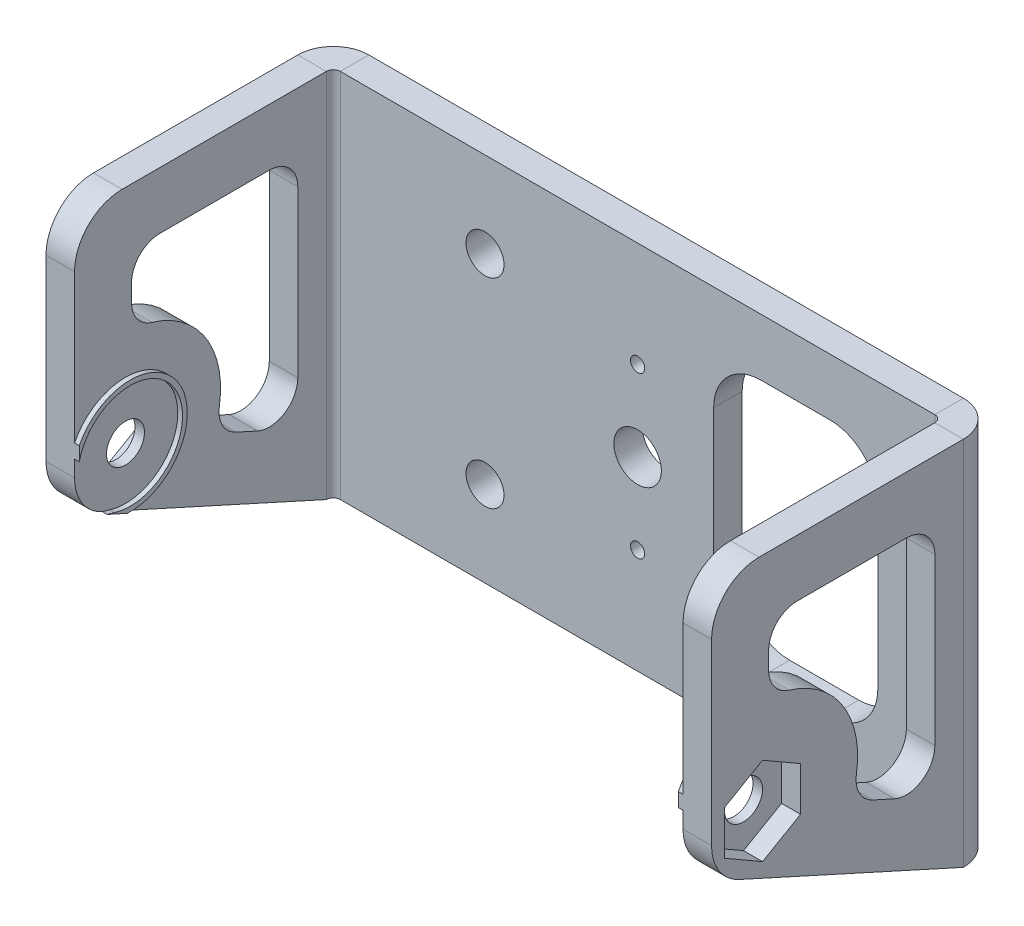
SolidWorks part; units mm, degrees
note: The reader was unsure of these and kept them because the rebuilt part matched: flange length of "Aresta-Flange1"; shared geometry of "Esboço13<3>".
ref_plane "Plano frontal" through (0, 0, 0) normal (0, 0, 1) x (1, 0, 0)
ref_plane "Plano superior" through (0, 0, 0) normal (0, 1, 0) x (1, 0, 0)
ref_plane "Plano direito" through (0, 0, 0) normal (1, 0, 0) x (0, 0, -1)
sketch "Esboço1" plane through (0, 0, 0) normal (0, 0, 1) x (1, 0, 0)
  line L1 (-37.0063, 15.0091) -> (26.9937, 15.0091)
  line L2 (-37.0063, 15.0091) -> (-37.0063, -23.9909)
  line L3 (-37.0063, -23.9909) -> (26.9937, -23.9909)
  line L4 (26.9937, 15.0091) -> (26.9937, -23.9909)
  dimension "D1" = 64
  dimension "D2" = 39
base flange "Flange-base1" sketch "Esboço1" thickness 3 reverse thickness direction no parameters "D1"=0.7366
sketch "Esboço6" plane through (0, 0, 0) normal (0, 0, 1) x (1, 0, 0)
  line L0 (-37.0063, -23.9909) -> (26.9937, 15.0091) construction
  line L1 (-21.0563, 6.0091) -> (11.0437, 6.0091)
  line L2 (-21.0563, 6.0091) -> (-21.0563, -14.9909)
  line L3 (-21.0563, -14.9909) -> (11.0437, -14.9909)
  line L4 (11.0437, 6.0091) -> (11.0437, -14.9909)
  line L5 (-37.0063, 15.0091) -> (26.9937, -23.9909) construction
  line L6 (26.9937, 15.0091) -> (-37.0063, 15.0091) construction
  line L7 (-37.0063, -23.9909) -> (26.9937, -23.9909) construction
  line L8 (-5.0063, 15.0091) -> (-5.0063, -23.9909) construction
  line L9 (-5.0063, 3.5238) -> (-5.0063, 12.5238) construction
  line L10 (-6.5063, 3.5238) -> (-6.5063, 12.5238)
  line L11 (-3.5063, 3.5238) -> (-3.5063, 12.5238)
  line L12 (-37.0063, -4.4909) -> (26.9937, -4.4909) construction
  line L13 (-37.0063, 15.0091) -> (-37.0063, -23.9909) construction
  line L14 (26.9937, -23.9909) -> (26.9937, 15.0091) construction
  line L15 (-5.0063, -12.5057) -> (-5.0063, -21.5057) construction
  line L16 (-6.5063, -12.5057) -> (-6.5063, -21.5057)
  line L17 (-3.5063, -12.5057) -> (-3.5063, -21.5057)
  circle A0 centre (-21.0563, 6.0091) radius 2
  circle A1 centre (-21.0563, -14.9909) radius 2
  circle A2 centre (11.0437, -14.9909) radius 2
  circle A3 centre (11.0437, 6.0091) radius 2
  circle A4 centre (-5.0063, -4.4909) radius 2.5
  arc A5 (-6.5063, 3.5238) -> (-3.5063, 3.5238) centre (-5.0063, 3.5238) ccw
  arc A6 (-3.5063, 12.5238) -> (-6.5063, 12.5238) centre (-5.0063, 12.5238) ccw
  arc A7 (-6.5063, -12.5057) -> (-3.5063, -12.5057) centre (-5.0063, -12.5057) cw
  arc A8 (-3.5063, -21.5057) -> (-6.5063, -21.5057) centre (-5.0063, -21.5057) cw
  circle A9 centre (-5.0063, -12.9409) radius 0.75
  circle A10 centre (-5.0063, 3.9591) radius 0.75
  point P18 (-5.0063, 8.0238)
  point P31 (-5.0063, -17.0057)
  dimension "D5" = 1.5
  dimension "D1" = 15.95
  dimension "D2" = 5
  dimension "D3" = 9
  dimension "D4" = 9
  dimension "D6" = 8.45
extrude "Corte-extrusão1" cut sketch "Esboço6" against normal blind 10 contours L1 A0 L2 | L2 A1 L3 | L3 A1 L2 | A4 | A9 | A10 | L2 A0 L1 | L16 A8 L17 A7
edge flange "Aresta-Flange1" sketch "Esboço11" flange profiles "Esboço11", "Esboço12" flange angle 90 flange length 30.22 flange position material outside bend radius 0.7366 thickness 3 parameters "D6"=10, "D8"=1
sketch "Esboço11" plane through (26.9937, 0, 0) normal (1, 0, 0) x (0, 1, 0)
  line L0 (-23.9909, 0) -> (15.0091, 0) construction
  line L1 (-23.9909, 0) -> (15.0091, 0)
  line L2 (-23.9909, 0) -> (-23.9909, 27.22)
  line L3 (-23.9909, 27.22) -> (15.0091, 27.22)
  line L4 (15.0091, 27.22) -> (15.0091, 0)
  dimension "D1" = 27.22
sketch "Esboço12" plane through (-37.0063, 0, 0) normal (-1, 0, 0) x (0, -1, 0)
  line L0 (-15.0091, 0) -> (23.9909, 0) construction
  line L1 (-15.0091, 0) -> (23.9909, 0)
  line L2 (-15.0091, 0) -> (-15.0091, 27.22)
  line L3 (-15.0091, 27.22) -> (23.9909, 27.22)
  line L4 (23.9909, 27.22) -> (23.9909, 0)
bend "DobradeAresta1" bend radius 0.7366 bend angle 90 parameters "D5"=1
bend "DobradeAresta2" bend radius 0.7366 bend angle 90 parameters "D5"=2
sketch "Esboço13" plane through (-40.0063, 0, 0) normal (-1, 0, 0) x (0, 0, 1)
  line L0 (0.7366, -23.9909) -> (27.22, -11.9909) construction
  line L1 (27.22, -23.9909) -> (27.22, 15.0091) construction
  line L2 (27.22, -11.9909) -> (0.7366, 15.0091) construction
  line L3 (0.7366, -23.9909) -> (27.22, -23.9909)
  line L4 (27.22, -23.9909) -> (27.22, -11.9909)
  line L5 (27.22, -11.9909) -> (0.7366, -23.9909)
  line L7 (17.86, -10.5964) -> (21.86, -12.9058)
  line L8 (21.86, -12.9058) -> (25.86, -10.5964)
  line L9 (25.86, -10.5964) -> (25.86, -5.9776)
  line L10 (25.86, -5.9776) -> (21.86, -3.6682)
  line L11 (21.86, -3.6682) -> (17.86, -5.9776)
  line L12 (17.86, -5.9776) -> (17.86, -10.5964)
  circle A0 centre (21.86, -8.287) radius 2
  circle A2 centre (21.86, -8.287) radius 4 construction
  point P12 (15.8204, -3.8404)
  dimension "D3" = 4
  dimension "D6" = 8
  dimension "D1" = 12
  dimension "D2" = 5.36
  dimension "D7" = 7.5
  dimension "D8" = 3.7039
extrude "Corte-extrusão2" cut sketch "Esboço13" against normal up to surface (70 mm away) contours A0 | L5 L3 L4 normal cut yes up to face at (29.9937, -4.4909, 13.9783)
fillet "Filete1" radius 5 4 edges at (28.4937, -11.9909, 27.22) (28.4937, 15.0091, 27.22) (-38.5063, -11.9909, 27.22) (-38.5063, 15.0091, 27.22)
extrude "Cut-Extrude1" cut sketch "Esboço13<3>" against normal blind 2 contours L11 L12 L7 L8 L9 L10 A0 normal cut yes
sketch "Esboço13<3>" plane through (-40.0063, 0, 0) normal (-1, 0, 0) x (0, 0, 1) same geometry as "Esboço13"
ref_plane "Plane1" through (-5.0063, 0, 0) normal (-1, 0, 0) x (0, -1, 0)
sketch "Sketch7" plane through (-37.0063, 0, 0) normal (1, 0, 0) x (0, 0, -1)
  line L0 (-24.2836, -13.3215) -> (-22.1704, -14.279)
  line L2 (-0.7366, -23.9909) -> (-24.2836, -13.3215) construction
  line L4 (-27.22, -8.7672) -> (-27.22, -5.5906)
  line L5 (-27.22, -8.7672) -> (-27.22, 10.0091) construction
  arc A0 (-22.1704, -14.279) -> (-27.22, -5.5906) centre (-21.86, -8.287) ccw
  arc A1 (-23.546, -13.5222) -> (-27.22, -7.054) centre (-21.86, -8.287) ccw
  arc A2 (-27.22, -8.7672) -> (-24.2836, -13.3215) centre (-22.22, -8.7672) ccw construction
  arc A3 (-27.22, -8.7672) -> (-24.2836, -13.3215) centre (-22.22, -8.7672) ccw
  arc A4 (-22.4908, -13.7507) -> (-24.2836, -13.3215) centre (-19.3008, 3.5311) cw
  dimension "D1" = 12
  dimension "D2" = 0.5
extrude "Boss-Extrude1" add sketch "Sketch7" along normal blind 0.5 contours A1 A4 L2 A0 A3
mirror "Mirror1" about plane through (-5.0063, 0, 0) normal (-1, 0, 0) of "Boss-Extrude1", "Cut-Extrude1"
sketch "Sketch15" plane through (0, 0, 0) normal (0, 0, 1) x (1, 0, 0)
  line L0 (26.2571, 15.0091) -> (-36.2697, 15.0091) construction
  line L1 (2.9937, 9.0091) -> (20.2571, 9.0091)
  line L2 (2.9937, 9.0091) -> (2.9937, -17.9909)
  line L3 (2.9937, -17.9909) -> (20.2571, -17.9909)
  line L4 (20.2571, 9.0091) -> (20.2571, -17.9909)
  line L5 (-36.2697, -23.9909) -> (26.2571, -23.9909) construction
  line L6 (26.2571, 15.0091) -> (26.2571, -23.9909) construction
  circle A0 centre (-5.0063, -4.4909) radius 2.5 construction
  dimension "D3" = 8
  dimension "D1" = 6
  dimension "D2" = 6
  dimension "D4" = 6
extrude "Cut-Extrude2" cut sketch "Sketch15" against normal up to surface (3 mm away) normal cut yes up to face at (-19.0563, 6.0091, -3)
fillet "Fillet1" radius 5 4 edges at (20.2571, -17.9909, -1.5) (2.9937, -17.9909, -1.5) (2.9937, 9.0091, -1.5) (20.2571, 9.0091, -1.5)
sketch "Sketch16" plane through (29.9937, 0, 0) normal (1, 0, 0) x (0, 0, -1)
  line L0 (-27.22, 10.0091) -> (-27.22, -8.7672) construction
  line L1 (-21.22, 9.0091) -> (-3.7366, 9.0091)
  line L2 (-21.22, 9.0091) -> (-21.22, 1.6925)
  line L3 (-12.5884, -12.0335) -> (-3.7366, -16.0444)
  line L4 (-3.7366, 9.0091) -> (-3.7366, -16.0444)
  line L5 (-0.7366, 15.0091) -> (-22.22, 15.0091) construction
  line L6 (-0.7366, 15.0091) -> (-0.7366, -23.9909) construction
  line L7 (-0.7366, -23.9909) -> (-24.2836, -13.3215) construction
  arc A0 (-12.5884, -12.0335) -> (-21.22, 1.6925) centre (-21.86, -8.287) ccw
  arc A1 (-22.1704, -14.279) -> (-27.22, -5.5906) centre (-21.86, -8.287) ccw construction
  dimension "D4" = 4
  dimension "D1" = 6
  dimension "D2" = 6
  dimension "D3" = 3
  dimension "D5" = 6
extrude "Cut-Extrude3" cut sketch "Sketch16" against normal up to surface (70 mm away) normal cut yes up to face at (-40.0063, -8.287, 21.86)
fillet "Fillet2" radius 3 10 edges at (-38.5063, 9.0091, 3.7366) (-38.5063, -16.0444, 3.7366) (-38.5063, -12.0335, 12.5884) (-38.5063, 1.6925, 21.22) (-38.5063, 9.0091, 21.22) (28.4937, -12.0335, 12.5884) (28.4937, -16.0444, 3.7366) (28.4937, 1.6925, 21.22) (28.4937, 9.0091, 21.22) (28.4937, 9.0091, 3.7366)
sketch "Curva-Linhas1" [suppressed] plane through (0, 0, 0) normal (0, 1, 0) x (1, 0, 0)
sketch "Caixa delimitadora1" [suppressed] plane through (0, 0, 0) normal (0, 1, 0) x (1, 0, 0)
sheet metal parameters "Chapa metálica1" thickness 3 parameters "D1"=0.7366
flat pattern "Padrão-Plano1" [suppressed]
sketch "Curva-Linhas2" plane through (0, 0, 0) normal (0, 1, 0) x (1, 0, 0)
sketch3d "Caixa delimitadora2" [suppressed]
  line L0 (-38.0063, -23.9909, 0) -> (26.9937, -23.9909, 0) construction
  line L1 (-38.0063, 15.0091, 0) -> (26.9937, 15.0091, 0) construction
  line L2 (-38.0063, -23.9909, 0) -> (-38.0063, 15.0091, 0) construction
  line L3 (26.9937, -23.9909, 0) -> (26.9937, 15.0091, 0) construction
sheet metal parameters "Chapa metálica2" thickness 3 parameters "D1"=0.7366
flat pattern "Padrão-Plano15"
sketch "Sketch13" plane through (0, 0, 0) normal (0, 1, 0) x (1, 0, 0)
sketch3d "Sketch14" [suppressed]
  line L0 (-38.0063, -23.9909, 0) -> (26.9937, -23.9909, 0) construction
  line L1 (-38.0063, 15.0091, 0) -> (26.9937, 15.0091, 0) construction
  line L2 (-38.0063, -23.9909, 0) -> (-38.0063, 15.0091, 0) construction
  line L3 (26.9937, -23.9909, 0) -> (26.9937, 15.0091, 0) construction
sheet metal parameters "Chapa metálica3" thickness 3 parameters "D1"=0.7366
flat pattern "Padrão-Plano1"
sketch "Curva-Linhas2" plane through (0, 0, 0) normal (0, 0, 1) x (1, 0, 0)
  line L0 (-39.0263, 15.0091) -> (-39.0263, -23.9909) construction
  line L1 (28.0138, -23.9909) -> (28.0138, 15.0091) construction
  line L2 (-39.0263, 15.0091) -> (-39.0263, -23.9909) construction
  line L3 (28.0138, -23.9909) -> (28.0138, 15.0091) construction
sketch3d "Caixa delimitadora2" [suppressed]
  line L0 (-67.2663, -23.9909, 0) -> (56.2538, -23.9909, 0) construction
  line L1 (-67.2663, 15.0091, 0) -> (56.2538, 15.0091, 0) construction
  line L2 (-67.2663, -23.9909, 0) -> (-67.2663, 15.0091, 0) construction
  line L3 (56.2538, -23.9909, 0) -> (56.2538, 15.0091, 0) construction
bend of the flat pattern "Planificar-<DobradeAresta1>1"
bend of the flat pattern "Planificar-<DobradeAresta2>1"
sheet metal parameters "Chapa metálica4" thickness 3 parameters "D1"=0.7366
flat pattern "Padrão-Plano1"
sketch "Curva-Linhas2" plane through (0, 0, 0) normal (0, 0, 1) x (1, 0, 0)
  line L0 (-39.0263, 15.0091) -> (-39.0263, -23.9909) construction
  line L1 (28.0138, -23.9909) -> (28.0138, 15.0091) construction
  line L2 (-39.0263, 15.0091) -> (-39.0263, -23.9909) construction
  line L3 (28.0138, -23.9909) -> (28.0138, 15.0091) construction
sketch3d "Caixa delimitadora2" [suppressed]
  line L0 (-67.2663, -23.9909, 0) -> (56.2538, -23.9909, 0) construction
  line L1 (-67.2663, 15.0091, 0) -> (56.2538, 15.0091, 0) construction
  line L2 (-67.2663, -23.9909, 0) -> (-67.2663, 15.0091, 0) construction
  line L3 (56.2538, -23.9909, 0) -> (56.2538, 15.0091, 0) construction
bend of the flat pattern "Planificar-<DobradeAresta1>1"
bend of the flat pattern "Planificar-<DobradeAresta2>1"
sheet metal parameters "Chapa metálica7" thickness 3 parameters "D1"=0.7366
flat pattern "Padrão-Plano7"
sketch "Curva-Linhas3" plane through (0, 0, 0) normal (0, 1, 0) x (1, 0, 0)
sketch3d "Caixa delimitadora3" [suppressed]
  line L0 (-24.309, -5.7376, 0) -> (-24.409, -10.7363, 0) construction
  line L1 (-19.3105, -5.8376, 0) -> (-19.4105, -10.8363, 0) construction
  line L2 (-24.309, -5.7376, 0) -> (-19.3105, -5.8376, 0) construction
  line L3 (-24.409, -10.7363, 0) -> (-19.4105, -10.8363, 0) construction
sheet metal parameters "Chapa metálica8" thickness 3 parameters "D1"=0.7366
flat pattern "Padrão-Plano8"
sketch "Curva-Linhas4" plane through (0, 0, 0) normal (0, 1, 0) x (1, 0, 0)
sketch "Caixa delimitadora4" [suppressed] plane through (0, 0, 0) normal (0, 1, 0) x (1, 0, 0)
sheet metal parameters "Chapa metálica9" thickness 3 parameters "D1"=0.7366
flat pattern "Padrão-Plano9"
sketch "Curva-Linhas5" plane through (0, 0, 0) normal (0, 1, 0) x (1, 0, 0)
sketch "Caixa delimitadora5" [suppressed] plane through (0, 0, 0) normal (0, 1, 0) x (1, 0, 0)
sheet metal parameters "Chapa metálica10" thickness 3 parameters "D1"=0.7366
flat pattern "Padrão-Plano1"
sketch "Curva-Linhas2" plane through (0, 0, 0) normal (0, 0, 1) x (1, 0, 0)
  line L0 (-39.0263, 15.0091) -> (-39.0263, -23.9909) construction
  line L1 (28.0138, -23.9909) -> (28.0138, 15.0091) construction
  line L2 (-39.0263, 15.0091) -> (-39.0263, -23.9909) construction
  line L3 (28.0138, -23.9909) -> (28.0138, 15.0091) construction
sketch3d "Caixa delimitadora2" [suppressed]
  line L0 (-67.2663, -23.9909, 0) -> (56.2538, -23.9909, 0) construction
  line L1 (-67.2663, 15.0091, 0) -> (56.2538, 15.0091, 0) construction
  line L2 (-67.2663, -23.9909, 0) -> (-67.2663, 15.0091, 0) construction
  line L3 (56.2538, -23.9909, 0) -> (56.2538, 15.0091, 0) construction
bend of the flat pattern "Planificar-<DobradeAresta1>1"
bend of the flat pattern "Planificar-<DobradeAresta2>1"
sheet metal parameters "Chapa metálica11" thickness 3 parameters "D1"=0.7366
flat pattern "Padrão-Plano1"
sketch "Curva-Linhas2" plane through (29.9937, 0, 0) normal (1, 0, 0) x (0, 0, -1)
  line L0 (67.0601, 15.0091) -> (67.0601, -23.9909) construction
  line L1 (1.02, 15.0091) -> (1.02, -23.9909) construction
  line L2 (67.0601, 15.0091) -> (67.0601, -23.9909) construction
  line L3 (1.02, 15.0091) -> (1.02, -23.9909) construction
sketch3d "Caixa delimitadora2" [suppressed]
  line L0 (95.3001, -23.9909, 0) -> (-27.22, -23.9909, 0) construction
  line L1 (95.3001, 15.0091, 0) -> (-27.22, 15.0091, 0) construction
  line L2 (95.3001, -23.9909, 0) -> (95.3001, 15.0091, 0) construction
  line L3 (-27.22, -23.9909, 0) -> (-27.22, 15.0091, 0) construction
bend of the flat pattern "Planificar-<DobradeAresta1>1"
bend of the flat pattern "Planificar-<DobradeAresta2>1"
sheet metal parameters "Chapa metálica12" thickness 3 parameters "D1"=0.7366
flat pattern "Padrão-Plano1"
sketch "Curva-Linhas2" plane through (0, 0, 0) normal (0, 0, 1) x (1, 0, 0)
  line L0 (-39.0263, 15.0091) -> (-39.0263, -23.9909) construction
  line L1 (28.0138, -23.9909) -> (28.0138, 15.0091) construction
  line L2 (-39.0263, 15.0091) -> (-39.0263, -23.9909) construction
  line L3 (28.0138, -23.9909) -> (28.0138, 15.0091) construction
sketch3d "Caixa delimitadora2" [suppressed]
  line L0 (-67.2663, -23.9909, 0) -> (56.2538, -23.9909, 0) construction
  line L1 (-67.2663, 15.0091, 0) -> (56.2538, 15.0091, 0) construction
  line L2 (-67.2663, -23.9909, 0) -> (-67.2663, 15.0091, 0) construction
  line L3 (56.2538, -23.9909, 0) -> (56.2538, 15.0091, 0) construction
bend of the flat pattern "Planificar-<DobradeAresta1>1"
bend of the flat pattern "Planificar-<DobradeAresta2>1"
sheet metal parameters "Chapa metálica13" thickness 3 parameters "D1"=0.7366
flat pattern "Padrão-Plano1"
sketch "Curva-Linhas2" plane through (0, 0, 0) normal (0, 1, 0) x (1, 0, 0)
sketch3d "Caixa delimitadora2" [suppressed]
  line L0 (-5.6795, -13.8101, 0) -> (-4.1876, -13.6647, 0) construction
  line L1 (-5.8248, -12.3188, 0) -> (-4.3328, -12.1735, 0) construction
  line L2 (-5.6795, -13.8101, 0) -> (-5.8248, -12.3188, 0) construction
  line L3 (-4.1876, -13.6647, 0) -> (-4.3328, -12.1735, 0) construction
sheet metal parameters "Chapa metálica14" thickness 3 parameters "D1"=0.7366
flat pattern "Padrão-Plano14"
sketch "Curva-Linhas7" plane through (0, 0, 0) normal (0, 1, 0) x (1, 0, 0)
sketch "Caixa delimitadora7" [suppressed] plane through (0, 0, 0) normal (0, 1, 0) x (1, 0, 0)
sheet metal parameters "Chapa metálica15" thickness 3 parameters "D1"=0.7366
flat pattern "Padrão-Plano1"
sketch "Curva-Linhas2" plane through (29.9937, 0, 0) normal (1, 0, 0) x (0, 0, -1)
  line L0 (67.0601, 15.0091) -> (67.0601, -23.9909) construction
  line L1 (1.02, 15.0091) -> (1.02, -23.9909) construction
  line L2 (67.0601, 15.0091) -> (67.0601, -23.9909) construction
  line L3 (1.02, 15.0091) -> (1.02, -23.9909) construction
sketch3d "Caixa delimitadora2" [suppressed]
  line L0 (95.3001, -23.9909, 0) -> (-27.22, -23.9909, 0) construction
  line L1 (95.3001, 15.0091, 0) -> (-27.22, 15.0091, 0) construction
  line L2 (95.3001, -23.9909, 0) -> (95.3001, 15.0091, 0) construction
  line L3 (-27.22, -23.9909, 0) -> (-27.22, 15.0091, 0) construction
bend of the flat pattern "Planificar-<DobradeAresta1>1"
bend of the flat pattern "Planificar-<DobradeAresta2>1"
sheet metal parameters "Chapa metálica16" thickness 3 parameters "D1"=0.7366
flat pattern "Padrão-Plano1"
sketch "Curva-Linhas2" plane through (29.9937, 0, 0) normal (1, 0, 0) x (0, 0, -1)
  line L0 (67.0601, 15.0091) -> (67.0601, -23.9909) construction
  line L1 (1.02, 15.0091) -> (1.02, -23.9909) construction
  line L2 (67.0601, 15.0091) -> (67.0601, -23.9909) construction
  line L3 (1.02, 15.0091) -> (1.02, -23.9909) construction
sketch3d "Caixa delimitadora2" [suppressed]
  line L0 (95.3001, -23.9909, 0) -> (-27.22, -23.9909, 0) construction
  line L1 (95.3001, 15.0091, 0) -> (-27.22, 15.0091, 0) construction
  line L2 (95.3001, -23.9909, 0) -> (95.3001, 15.0091, 0) construction
  line L3 (-27.22, -23.9909, 0) -> (-27.22, 15.0091, 0) construction
bend of the flat pattern "Planificar-<DobradeAresta1>1"
bend of the flat pattern "Planificar-<DobradeAresta2>1"
